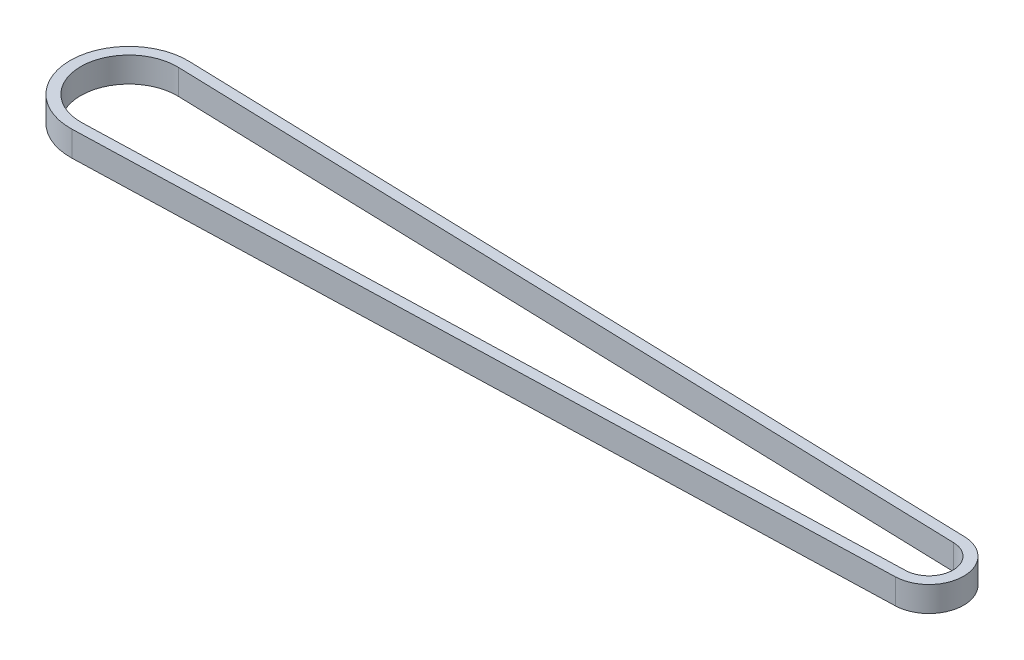
SolidWorks part; units mm, degrees
material "POLYURETHANE (11671)"
ref_plane "Front Plane" through (0, 0, 0) normal (0, 0, 1) x (1, 0, 0)
ref_plane "Top Plane" through (0, 0, 0) normal (0, 1, 0) x (1, 0, 0)
ref_plane "Right Plane" through (0, 0, 0) normal (1, 0, 0) x (0, 0, -1)
sketch "Sketch1" plane through (0, 0, 0) normal (0, 1, 0) x (1, 0, 0)
  line L0 (-95.25, 0) -> (95.25, 0) construction
  line L1 (0, 0) -> (0, 67523.6974) construction
  line L4 (-94.9057, 11.4502) -> (95.4222, 5.7264)
  line L5 (-94.9057, -11.4502) -> (95.4222, -5.7264)
  line L6 (0, 0) -> (0, 44.9411) construction
  line L7 (-94.8309, 13.9637) -> (95.4977, 8.2513)
  line L8 (-94.8309, -13.9637) -> (95.4977, -8.2513)
  arc A0 (-94.9057, 11.4502) -> (-94.9057, -11.4502) centre (-95.25, 0) ccw
  arc A1 (95.4222, -5.7264) -> (95.4222, 5.7264) centre (95.25, 0) ccw
  arc A2 (-94.8309, 13.9637) -> (-94.8309, -13.9637) centre (-95.25, 0) ccw
  arc A3 (95.4977, -8.2513) -> (95.4977, 8.2513) centre (95.25, 0) ccw
  dimension "D2" = 22.9108
  dimension "D3" = 11.4579
  dimension "D4" = 27.94
  dimension "D5" = 16.51
  dimension "D1" = 190.5
extrude "Boss-Extrude1" add sketch "Sketch1" along normal blind 5.9944
